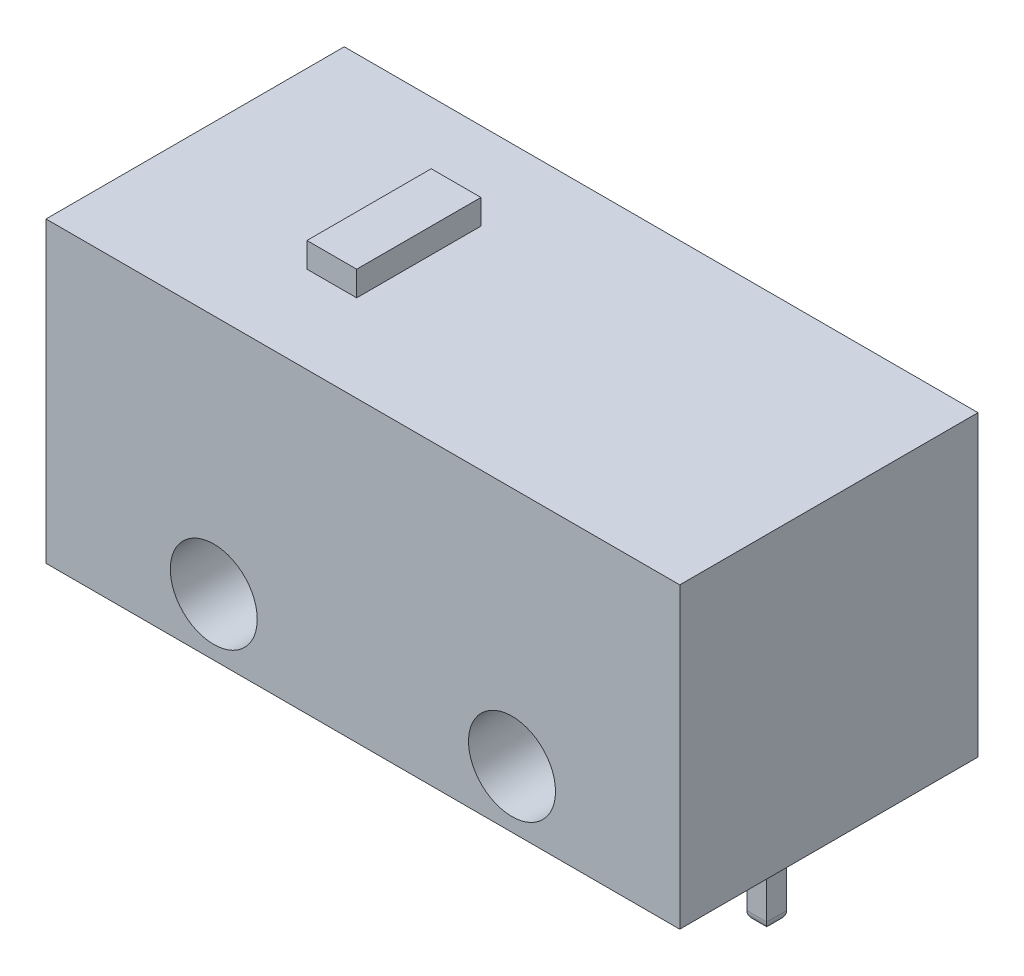
SolidWorks part; units mm, degrees
ref_plane "Płaszczyzna przednia" through (0, 0, 0) normal (0, 0, 1) x (1, 0, 0)
ref_plane "Płaszczyzna górna" through (0, 0, 0) normal (0, 1, 0) x (1, 0, 0)
ref_plane "Płaszczyzna prawa" through (0, 0, 0) normal (1, 0, 0) x (0, 0, -1)
sketch "Sketch1" plane through (0, 0, 0) normal (0, 0, 1) x (1, 0, 0)
  line L1 (0, 0) -> (12.75, 0)
  line L2 (0, 0) -> (0, 6)
  line L3 (0, 6) -> (12.75, 6)
  line L4 (12.75, 0) -> (12.75, 6)
  line L5 (0, 0) -> (12.75, 6) construction
  line L6 (0, 6) -> (12.75, 0) construction
  point P4 (6.375, 3)
  dimension "D1" = 12.75
  dimension "D2" = 6
extrude "Boss-Extrude1" add sketch "Sketch1" along normal blind 6
hole_wizard "Ø1.0mm Dowel Hole1" positions "Sketch2" profile "Sketch3" hole size "Ø1.0" standard "ANSI Metric" end condition through all
sketch "Sketch2" plane through (0, 0, 6) normal (0, 0, 1) x (1, 0, 0)
  line L0 (0, 0) -> (12.75, 0) construction
  line L1 (0, 6) -> (0, 0) construction
  line L2 (12.75, 0) -> (12.75, 6) construction
  point P0 (3.375, 1.15)
  point P2 (9.375, 1.15)
  dimension "D1" = 6
  dimension "D2" = 1.15
  dimension "D3" = 3.375
  dimension "D4" = 3.375
sketch "Sketch3" plane through (3.375, 1.15, 6) normal (1, 0, 0) x (0, -1, 0)
  line L0 (0, 0) -> (0, 6)
  line L1 (0, 6) -> (0.875, 6)
  line L2 (0.875, 6) -> (0.875, 0)
  line L5 (0.875, 0) -> (0, 0)
  line L11 (0, -6.35) -> (0, 107.95) construction
  dimension "Thru Hole Dia." = 1.75
  dimension "Thru Hole Depth" = 6
sketch "Sketch4" plane through (0, 6, 0) normal (0, 1, 0) x (1, 0, 0)
  line L0 (12.75, 0) -> (0, 0) construction
  line L1 (3.5, -1.75) -> (4.5, -1.75)
  line L2 (3.5, -1.75) -> (3.5, -4.25)
  line L3 (3.5, -4.25) -> (4.5, -4.25)
  line L4 (4.5, -1.75) -> (4.5, -4.25)
  line L5 (3.5, -1.75) -> (4.5, -4.25) construction
  line L6 (3.5, -4.25) -> (4.5, -1.75) construction
  line L7 (0, -6) -> (0, 0) construction
  point P4 (4, -3)
  dimension "D1" = 1
  dimension "D2" = 2.5
  dimension "D3" = 1.75
  dimension "D4" = 3.5
extrude "Boss-Extrude2" add sketch "Sketch4" along normal blind 0.5
ref_plane "Plane1" through (0, 0, 1) normal (0, 0, -1) x (-1, 0, 0)
sketch "Sketch5" plane through (0, 0, 1) normal (0, 0, -1) x (-1, 0, 0)
  line L0 (-1.3, 6) -> (-13.9, 9.1415)
  line L1 (-12.75, 6) -> (0, 6) construction
  dimension "D1" = 14
  dimension "D2" = 1.3
  dimension "D3" = 12.6
  dimension "D4" = 3.1415
extrude "Extrude-Thin3" [suppressed] add sketch "Sketch5" against normal blind 4 separate body thin thin type one direction wall 0.15
sketch "Sketch6" [suppressed] plane through (-1.3686, 5.4892, 0) normal (-0.2419, 0.9703, 0) x (0.9703, 0.2419, 0)
  line L1 (2.7129, -2.625) -> (10.0129, -2.625)
  line L2 (2.7129, -2.625) -> (2.7129, -3.375)
  line L3 (2.7129, -3.375) -> (10.0129, -3.375)
  line L4 (15.6986, -1) -> (2.7129, -1)
  line L5 (2.7129, -1) -> (2.7129, -5)
  line L6 (2.7129, -5) -> (15.6986, -5)
  line L7 (15.6986, -5) -> (15.6986, -1)
  line L8 (15.6986, -1) -> (2.7129, -1)
  line L9 (2.7129, -1) -> (2.7129, -5)
  line L10 (2.7129, -5) -> (15.6986, -5)
  line L11 (15.6986, -5) -> (15.6986, -1)
  line L12 (10.0129, -2.625) -> (10.0129, -3.375)
  line L13 (2.7129, -2.625) -> (10.0129, -3.375) construction
  line L14 (2.7129, -3.375) -> (10.0129, -2.625) construction
  point P8 (6.3629, -3)
  line M9 (2.7129, -1) -> (2.7129, -5)
  dimension "D2" = 7.3
  dimension "D3" = 0.75
  dimension "D4" = 1.625
  dimension "D1" = 0
extrude "Cut-Extrude1" [suppressed] cut sketch "Sketch6" against normal blind 0.15 contours L12 L1 L3 M9
fillet "Fillet6" [suppressed] radius 0.15
fillet "Fillet7" [suppressed] radius 0.375
fillet "Fillet8" [suppressed] radius 0.375
sketch "Sketch7" plane through (0, 0, 0) normal (0, -1, 0) x (1, 0, 0)
  line L0 (0, 6) -> (12.75, 6) construction
  line L1 (0, 6) -> (0, 0) construction
  line L2 (12.75, 6) -> (12.75, 0) construction
  line L3 (11.7, 3) -> (11.3, 3)
  line L4 (6.175, 3) -> (6.575, 3)
  line L5 (1.05, 3) -> (1.45, 3)
  point P0 (1.25, 3)
  point P1 (6.375, 3)
  point P2 (11.5, 3)
  point P11 (6.375, 3)
  point P12 (1.25, 3)
  point P30 (11.5, 3)
  dimension "D1" = 3
  dimension "D2" = 1.25
  dimension "D3" = 1.25
  dimension "D4" = 6.375
  dimension "D5" = 0.4
  dimension "D6" = 0.4
  dimension "D7" = 0.4
extrude "Extrude-Thin6" add sketch "Sketch7" along normal blind 2 thin thin type mid plane wall 0.4
fillet "Fillet9" radius 0.2 12 edges at (11.7, -2, 3) (11.5, -2, 2.8) (11.3, -2, 3) (11.5, -2, 3.2) (6.175, -2, 3) (6.375, -2, 3.2) (6.575, -2, 3) (6.375, -2, 2.8) (1.05, -2, 3) (1.25, -2, 3.2) (1.45, -2, 3) (1.25, -2, 2.8)
